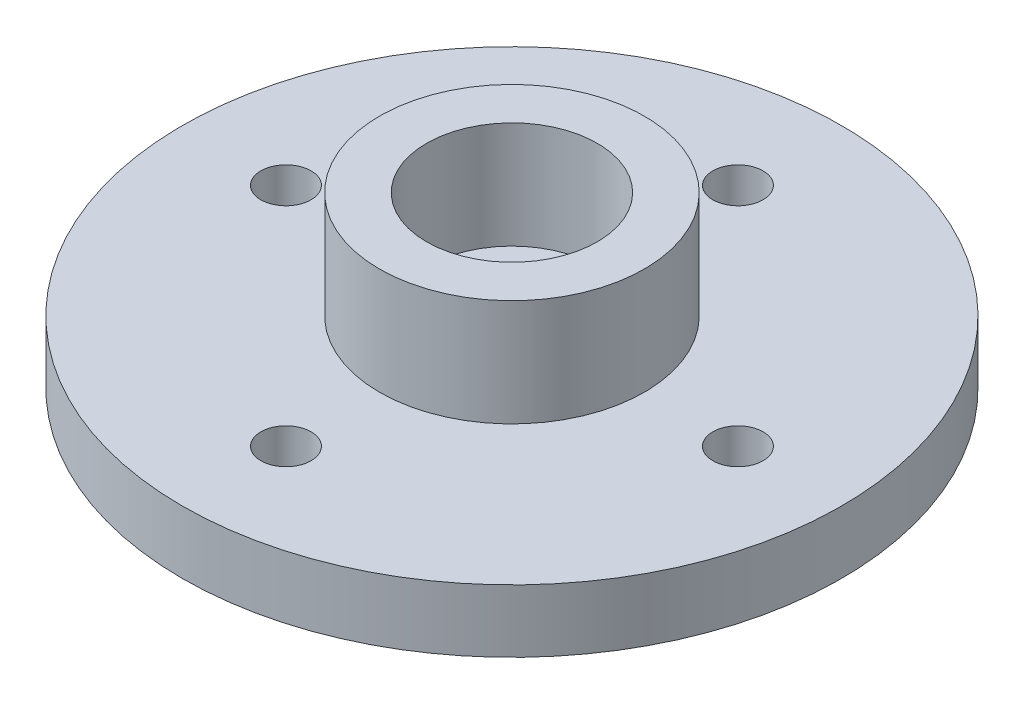
SolidWorks part; units mm, degrees
ref_plane "Front Plane" through (0, 0, 0) normal (0, 0, 1) x (1, 0, 0)
ref_plane "Top Plane" through (0, 0, 0) normal (0, 1, 0) x (1, 0, 0)
ref_plane "Right Plane" through (0, 0, 0) normal (1, 0, 0) x (0, 0, -1)
sketch "Sketch1" plane through (0, 0, 0) normal (0, 1, 0) x (1, 0, 0)
  circle A0 centre (0, 0) radius 10.5
  circle A1 centre (0, 7.2) radius 0.8
  circle A2 centre (7.2, 0) radius 0.8
  circle A3 centre (0, -7.2) radius 0.8
  circle A4 centre (-7.2, 0) radius 0.8
  point P14 (0, 0)
  dimension "D1" = 4
extrude "Boss-Extrude1" add sketch "Sketch1" along normal blind 2
sketch "Sketch2" plane through (0, 2, 0) normal (0, 1, 0) x (1, 0, 0)
  circle A0 centre (0, 0) radius 4.22
  circle A1 centre (0, 0) radius 2.72
  circle A2 centre (0, 0) radius 1.5
  dimension "D1" = 1.5
extrude "Cut-Extrude1" cut sketch "Sketch2" against normal blind 2 contours A2 region at (0, 2, 0)
extrude "Boss-Extrude2" add sketch "Sketch2<3>" along normal blind 3.4 contours A0 A1 region at (-4.1006, 2, 0)
sketch "Sketch2<3>" plane through (0, 2, 0) normal (0, 1, 0) x (1, 0, 0) same geometry as "Sketch2"
